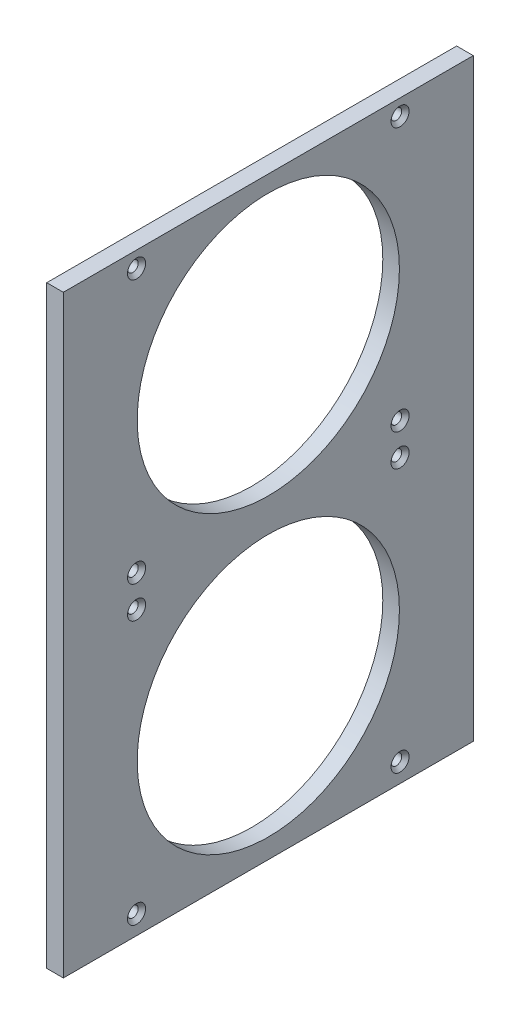
SolidWorks part; units mm, degrees
ref_plane "Front Plane" through (0, 0, 0) normal (0, 0, 1) x (1, 0, 0)
ref_plane "Top Plane" through (0, 0, 0) normal (0, 1, 0) x (1, 0, 0)
ref_plane "Right Plane" through (0, 0, 0) normal (1, 0, 0) x (0, 0, -1)
sketch "Sketch1" plane through (0, 0, 0) normal (0, 1, 0) x (1, 0, 0)
  line L1 (-83.25, 55.5) -> (83.25, 55.5)
  line L2 (-83.25, 55.5) -> (-83.25, -55.5)
  line L3 (-83.25, -55.5) -> (83.25, -55.5)
  line L4 (83.25, 55.5) -> (83.25, -55.5)
  line L5 (-83.25, 55.5) -> (83.25, -55.5) construction
  line L6 (-83.25, -55.5) -> (83.25, 55.5) construction
  point P0 (0, 0)
  dimension "D1" = 166.5
  dimension "D2" = 111
extrude "Boss-Extrude1" add sketch "Sketch1" along normal blind 30.5
shell "Shell1" thickness 4.5 removed face at (-83.25, 15.25, 0) removed face at (0, 30.5, 0)
sketch "Sketch2" plane through (0, 4.5, 0) normal (0, 1, 0) x (1, 0, 0)
  line L5 (78.75, 51) -> (-83.25, 51) construction
  line L6 (-78.25, 46) -> (78.75, 46)
  line L9 (-78.25, 46) -> (-78.25, -46)
  line L10 (-78.25, -46) -> (78.75, -46)
  line L11 (78.75, 46) -> (78.75, -46)
  line L12 (-83.25, -51) -> (78.75, -51) construction
  line L13 (-83.25, 51) -> (-83.25, -51) construction
  line L14 (78.75, -51) -> (78.75, 51) construction
  point P0 (0, 0)
  dimension "D1" = 5
  dimension "D2" = 5
  dimension "D3" = 5
extrude "Cut-Extrude1" cut sketch "Sketch2" against normal up to next
hole_wizard "Tap Drill for #6-32 Tap1" positions "Sketch4" profile "Sketch5" hole size "#6-32" standard "ANSI Inch" end condition up to next
sketch "Sketch4" plane through (0, 0, -55.5) normal (0, 0, -1) x (-1, 0, 0)
  line L0 (-78.75, 4.5) -> (83.25, 4.5) construction
  line L2 (-78.75, 30.5) -> (-78.75, 4.5) construction
  point P0 (47.66, 10.84)
  point P2 (-53.75, 10.84)
  dimension "D1" = 6.34
  dimension "D2" = 25
  dimension "D3" = 101.41
sketch "Sketch5" plane through (-47.66, 10.84, -55.5) normal (1, 0, 0) x (0, 1, 0)
  line L0 (0, 0) -> (0, 4.5)
  line L1 (0, 4.5) -> (1.4503, 4.5)
  line L2 (1.4503, 4.5) -> (1.4503, 0)
  line L5 (1.4503, 0) -> (0, 0)
  line L11 (0, -6.35) -> (0, 107.95) construction
  dimension "Thru Hole Dia." = 2.9007
  dimension "Thru Hole Depth" = 4.5
mirror "Mirror1" about plane through (0, 0, 0) normal (0, 0, 1) of "Tap Drill for #6-32 Tap1"
pattern_linear "LPattern1" count 8 spacing 30.5 along (0, 1, 0) of bodies 104
combine bodies "Combine1" operation type add bodies to combine 104 105
sketch "Sketch7" plane through (-83.25, 0, 0) normal (-1, 0, 0) x (0, 0, 1)
  line L1 (-51, 30.5) -> (51, 30.5)
  line L2 (-51, 30.5) -> (-51, 35)
  line L3 (-51, 35) -> (51, 35)
  line L4 (51, 30.5) -> (51, 35)
extrude "Cut-Extrude2" cut sketch "Sketch7" against normal up to surface (5 mm away) up to face at (-78.25, 32.75, 0)
combine bodies "Combine2" operation type add bodies to combine 109 110 112 111 114 108 113
sketch "Sketch8" plane through (-83.25, 0, 0) normal (-1, 0, 0) x (0, 0, 1)
  line L1 (-51, 61) -> (51, 61)
  line L2 (-51, 61) -> (-51, 218)
  line L3 (-51, 218) -> (51, 218)
  line L4 (51, 61) -> (51, 218)
extrude "Cut-Extrude3" cut sketch "Sketch8" against normal up to surface (5 mm away) up to face at (-78.25, 215.75, 0)
sketch "Sketch9" plane through (83.25, 0, 0) normal (1, 0, 0) x (0, 0, -1)
  line L0 (-55.5, 244) -> (55.5, 244) construction
  line L1 (-40, 244) -> (40, 244) construction
  line L2 (-40, 244) -> (-40, 4) construction
  line L3 (-40, 4) -> (40, 4) construction
  line L4 (40, 244) -> (40, 4) construction
  line L5 (0, 244) -> (0, 4) construction
  line L6 (-40, 164) -> (40, 164) construction
  line L7 (-40, 84) -> (40, 84) construction
  circle A0 centre (0, 204) radius 35.5
  circle A1 centre (0, 124) radius 35.5
  circle A2 centre (0, 44) radius 35.5
  dimension "D5" = 71
  dimension "D7" = 71
  dimension "D8" = 71
  dimension "D1" = 240
  dimension "D2" = 80
  dimension "D3" = 80
  dimension "D4" = 80
  dimension "D6" = 40
  dimension "D9" = 40
extrude "Cut-Extrude4" cut sketch "Sketch9" against normal up to next
sketch "Fan Dimensions" plane through (83.25, 0, 0) normal (1, 0, 0) x (0, 0, -1)
  line L0 (0, 239.5) -> (0, 168.5) construction
  line L1 (-40, 204) -> (40, 204) construction
  line L2 (-40, 244) -> (40, 244) construction
  line L3 (-40, 244) -> (-40, 164) construction
  line L4 (-40, 164) -> (40, 164) construction
  line L5 (40, 244) -> (40, 164) construction
  line L6 (-40, 244) -> (40, 164) construction
  line L7 (-40, 164) -> (40, 244) construction
  circle A0 centre (0, 204) radius 35.5 construction
  circle A1 centre (-35.675, 239.675) radius 2.175
  circle A2 centre (35.675, 239.675) radius 2.175
  circle A3 centre (35.675, 168.325) radius 2.175
  circle A4 centre (-35.675, 168.325) radius 2.175
  point P5 (0, 204)
  dimension "D2" = 80
  dimension "D3" = 4.35
  dimension "D1" = 80
  dimension "D4" = 4.325
hole_wizard "Tap Drill for #6-32 Tap2" positions "Sketch11" profile "Sketch12" hole size "#6-32" standard "ANSI Inch" end condition up to next
sketch "Sketch11" plane through (83.25, 0, 0) normal (1, 0, 0) x (0, 0, -1)
  point P0 (-35.675, 239.675)
  point P3 (35.675, 239.675)
  point P6 (35.675, 168.325)
  point P9 (-35.675, 168.325)
sketch "Sketch12" plane through (83.25, 239.675, 35.675) normal (0, 1, 0) x (0, 0, -1)
  line L0 (0, 0) -> (0, 4.5)
  line L1 (0, 4.5) -> (1.4503, 4.5)
  line L2 (1.4503, 4.5) -> (1.4503, 0)
  line L5 (1.4503, 0) -> (0, 0)
  line L11 (0, -6.35) -> (0, 107.95) construction
  dimension "Thru Hole Dia." = 2.9007
  dimension "Thru Hole Depth" = 4.5
ref_plane "Plane1" through (0, 164, 0) normal (0, 1, 0) x (1, 0, 0)
mirror "Mirror2" about plane through (0, 164, 0) normal (0, 1, 0) of "Tap Drill for #6-32 Tap2"
ref_plane "Plane2" through (0, 124, 0) normal (0, 1, 0) x (1, 0, 0)
mirror "Mirror3" about plane through (0, 124, 0) normal (0, 1, 0) of "Tap Drill for #6-32 Tap2"
sketch "Sketch13" plane through (0, 0, 0) normal (0, -1, 0) x (1, 0, 0)
  line L0 (83.25, 55.5) -> (83.25, -55.5) construction
  line L1 (-83.25, -55.5) -> (83.25, -55.5)
  line L2 (-83.25, -55.5) -> (-83.25, -147.5)
  line L3 (-83.25, -147.5) -> (83.25, -147.5)
  line L4 (83.25, -55.5) -> (83.25, -147.5)
  dimension "D1" = 92
extrude "Boss-Extrude2" add sketch "Sketch13" against normal blind 4.5
ref_plane "Plane3" through (0, 0, -101.5) normal (0, 0, -1) x (-1, 0, 0)
mirror "Mirror4" about plane through (0, 0, -101.5) normal (0, 0, -1) of bodies 122 125
sketch "Sketch17" plane through (-78.25, 0, 0) normal (-1, 0, 0) x (0, 0, 1)
  line L0 (-46, 35) -> (-51, 30.5)
  line L1 (-51, 30.5) -> (-46, 30.5)
  line L2 (-46, 30.5) -> (-46, 35)
  line L3 (-51, 61) -> (-46, 65.5)
  line L4 (-46, 65.5) -> (-46, 61)
  line L5 (-46, 61) -> (-51, 61)
  line L6 (-51, 91.5) -> (-46, 96)
  line L7 (-46, 96) -> (-46, 91.5)
  line L8 (-46, 91.5) -> (-51, 91.5)
  line L9 (-51, 122) -> (-46, 126.5)
  line L10 (-46, 126.5) -> (-46, 122)
  line L11 (-46, 122) -> (-51, 122)
  line L12 (-51, 152.5) -> (-46, 157)
  line L13 (-46, 157) -> (-46, 152.5)
  line L14 (-46, 152.5) -> (-51, 152.5)
  line L15 (-51, 183) -> (-46, 187.5)
  line L16 (-46, 187.5) -> (-46, 183)
  line L17 (-46, 183) -> (-51, 183)
  line L18 (-51, 213.5) -> (-46, 218)
  line L19 (-46, 218) -> (-46, 213.5)
  line L20 (-46, 213.5) -> (-51, 213.5)
extrude "Cut-Extrude7" cut sketch "Sketch17" against normal up to surface (157 mm away) up to face at (78.75, 8.325, 37.1253)
mirror "Mirror5" about plane through (0, 0, 0) normal (0, 0, 1) of "Cut-Extrude7"
mirror "Mirror6" about plane through (0, 0, -101.5) normal (0, 0, -1) of "Mirror5", "Cut-Extrude7"
sketch "Sketch31" plane through (0, 4.5, 0) normal (0, 1, 0) x (1, 0, 0)
  line L1 (-83.25, 254) -> (-78.25, 254)
  line L2 (-83.25, 254) -> (-83.25, 152)
  line L3 (-83.25, 152) -> (-78.25, 152)
  line L4 (-78.25, 254) -> (-78.25, 152)
  line L5 (-83.25, 51) -> (-78.25, 51)
  line L6 (-83.25, 51) -> (-83.25, -51)
  line L7 (-83.25, -51) -> (-78.25, -51)
  line L8 (-78.25, 51) -> (-78.25, -51)
extrude "Cut-Extrude11" cut sketch "Sketch31" against normal up to next
sketch "Sketch33" plane through (83.25, 0, 0) normal (1, 0, 0) x (0, 0, -1)
  line L1 (147.5, 4.5) -> (143, 4.5)
  line L2 (147.5, 4.5) -> (147.5, 153.7)
  line L3 (147.5, 153.7) -> (143, 153.7)
  line L4 (143, 4.5) -> (143, 153.7)
  dimension "D1" = 4.5
  dimension "D2" = 149.2
extrude "Boss-Extrude3" add sketch "Sketch33" against normal blind 4.5
pattern_linear "LPattern2" count 3 spacing 81 along (-1, 0, 0) of "Boss-Extrude3"
sketch "Sketch34" plane through (-83.25, 0, 0) normal (-1, 0, 0) x (0, 0, 1)
  line L0 (-147.5, 153.7) -> (-147.5, 0) construction
  line L1 (-152, 0) -> (-51, 0) construction
  line L2 (-143, 25) -> (-147.5, 25)
  line L3 (-143, 153.7) -> (-143, 4.5) construction
  line L4 (-147.5, 25) -> (-147.5, 76.85)
  line L5 (-147.5, 76.85) -> (-143, 81.35)
  line L6 (-143, 81.35) -> (-143, 25)
  line L7 (-143, 89.35) -> (-147.5, 89.35)
  line L8 (-147.5, 89.35) -> (-147.5, 141.2)
  line L9 (-147.5, 141.2) -> (-143, 145.7)
  line L10 (-143, 145.7) -> (-143, 89.35)
  line L11 (-147.5, 153.7) -> (-143, 153.7) construction
  line L12 (-55.5, 4.5) -> (-143, 4.5) construction
  line L13 (-147.5, 25) -> (-143, 25)
  line L14 (-147.5, 25) -> (-147.5, 13.5)
  line L15 (-147.5, 13.5) -> (-143, 13.5)
  line L16 (-143, 25) -> (-143, 13.5)
  line M20 (-143, 4.5) -> (-143, 153.7)
  dimension "D1" = 45
  dimension "D2" = 45
  dimension "D3" = 8
  dimension "D4" = 8
  dimension "D5" = 9
extrude "Cut-Extrude12" cut sketch "Sketch34" against normal up to surface (85.5 mm away) contours L5 L4 L2 M20 | L14 L15 L2 M20 | L10 L7 L8 L9 up to face at (2.25, 79.1, -145.25)
sketch "Sketch35" plane through (78.75, 0, 0) normal (-1, 0, 0) x (0, 0, 1)
  line L4 (-147.5, 153.7) -> (-147.5, 4.5)
  line L5 (-147.5, 4.5) -> (-143, 4.5)
  line L6 (-143, 4.5) -> (-143, 153.7)
  line L7 (-143, 153.7) -> (-147.5, 153.7)
  line L8 (-147.5, 153.7) -> (-147.5, 4.5)
  line L9 (-147.5, 4.5) -> (-143, 4.5)
  line L10 (-143, 4.5) -> (-143, 153.7)
  line L11 (-143, 153.7) -> (-147.5, 153.7)
  dimension "D1" = 0
extrude "Boss-Extrude4" add sketch "Sketch35" along normal blind 4.5
sketch "Sketch36" plane through (83.25, 0, 0) normal (1, 0, 0) x (0, 0, -1)
  line L0 (147.5, 153.7) -> (55.5, 153.7) construction
  line L1 (55.5, 4.5) -> (69.5, 4.5)
  line L2 (55.5, 4.5) -> (55.5, 42.5)
  line L3 (55.5, 42.5) -> (69.5, 42.5)
  line L4 (69.5, 4.5) -> (69.5, 42.5)
  line L5 (55.5, 244) -> (55.5, 4.5) construction
  line L7 (55.5, 153.7) -> (79.5, 153.7)
  line L8 (55.5, 153.7) -> (55.5, 141.7)
  line L9 (55.5, 141.7) -> (79.5, 141.7)
  line L10 (79.5, 153.7) -> (79.5, 141.7)
  line L11 (143, 153.7) -> (131, 153.7)
  line L12 (143, 153.7) -> (143, 139.7)
  line L13 (143, 139.7) -> (131, 139.7)
  line L14 (131, 153.7) -> (131, 139.7)
  line L15 (143, 4.5) -> (129, 4.5)
  line L16 (143, 4.5) -> (143, 16.5)
  line L17 (143, 16.5) -> (129, 16.5)
  line L18 (129, 4.5) -> (129, 16.5)
  dimension "D1" = 14
  dimension "D2" = 38
  dimension "D3" = 24
  dimension "D4" = 12
  dimension "D5" = 12
  dimension "D6" = 14
  dimension "D7" = 14
  dimension "D8" = 12
extrude "Boss-Extrude5" add sketch "Sketch36" against normal blind 4.5
sketch "Sketch37" plane through (83.25, 0, 0) normal (1, 0, 0) x (0, 0, -1)
  line L0 (55.5, 244) -> (55.5, 153.7) construction
  line L1 (79.5, 153.7) -> (55.5, 153.7) construction
  line L2 (143, 139.7) -> (143, 16.5) construction
  line L3 (55.5, 141.7) -> (55.5, 42.5) construction
  line L4 (129, 4.5) -> (69.5, 4.5) construction
  circle A0 centre (71.32, 147.92) radius 1.45
  circle A1 centre (137.68, 147.92) radius 1.45
  circle A2 centre (61.57, 34.51) radius 1.45
  circle A3 centre (137.55, 10.15) radius 1.45
  dimension "D1" = 2.9
  dimension "D4" = 2.9
  dimension "D6" = 2.9
  dimension "D9" = 2.9
  dimension "D2" = 15.82
  dimension "D3" = 5.78
  dimension "D5" = 5.32
  dimension "D7" = 6.07
  dimension "D8" = 30.01
  dimension "D10" = 5.65
  dimension "D11" = 5.45
extrude "Cut-Extrude13" cut sketch "Sketch37" against normal up to next
sketch "Sketch38" plane through (83.25, 0, 0) normal (1, 0, 0) x (0, 0, -1)
  line L0 (79.5, 141.7) -> (55.5, 117.7)
  line L1 (55.5, 141.7) -> (55.5, 42.5) construction
  line L2 (55.5, 117.7) -> (55.5, 141.7)
  line L3 (55.5, 141.7) -> (79.5, 141.7)
  line L4 (131, 139.7) -> (143, 127.7)
  line L5 (143, 139.7) -> (143, 16.5) construction
  line L6 (143, 127.7) -> (143, 139.7)
  line L7 (143, 139.7) -> (131, 139.7)
  dimension "D1" = 45
  dimension "D2" = 45
extrude "Boss-Extrude6" add sketch "Sketch38" along normal up to surface (4.5 mm away)
sketch "Sketch39" plane through (83.25, 0, 0) normal (1, 0, 0) x (0, 0, -1)
  circle A0 centre (71.32, 147.92) radius 3.5
  circle A1 centre (137.68, 147.92) radius 3.5
  circle A2 centre (137.55, 10.15) radius 3.5
  circle A3 centre (61.57, 34.51) radius 3.5
  dimension "D1" = 7
  dimension "D2" = 7
  dimension "D3" = 7
  dimension "D4" = 7
extrude "Cut-Extrude14" cut sketch "Sketch39" against normal blind 2.5 draft 39
chamfer "Chamfer1" distance 4.5 angle 45 4 edges at (81, 16.5, -129) (81, 153.7, -131) (81, 153.7, -79.5) (81, 42.5, -69.5)
sketch "Sketch41" plane through (0, 0, 0) normal (0, -1, 0) x (1, 0, 0)
  line L1 (-83.25, 55.5) -> (83.25, 55.5)
  line L2 (-83.25, 55.5) -> (-83.25, -258.5)
  line L3 (-83.25, -258.5) -> (83.25, -258.5)
  line L4 (83.25, 55.5) -> (83.25, -258.5)
extrude "Boss-Extrude7" add sketch "Sketch41" along normal blind 4.5
sketch "Sketch42" plane through (0, 0, 0) normal (0, 1, 0) x (1, 0, 0)
  line L0 (-43.855, 38) -> (43.855, 38)
  line L1 (45.3708, 32.4111) -> (1.5158, 6.7345)
  line L2 (-1.5158, 6.7345) -> (-45.3708, 32.4111)
  line L3 (10.2688, 2.5889) -> (66.2342, 35.3561)
  line L4 (70.75, 32.7672) -> (70.75, -32.7672)
  line L5 (66.2342, -35.3561) -> (10.2688, -2.5889)
  line L7 (78.75, -51) -> (78.75, 51) construction
  line L8 (78.75, 46) -> (-78.25, 46) construction
  line L9 (78.75, -46) -> (-78.25, -46) construction
  line L10 (0, 5.847) -> (0, 0) construction
  line L11 (0, 0) -> (5.847, 0) construction
  line L12 (-83.25, 0) -> (70.75, 0) construction
  line L13 (-83.25, -51) -> (-83.25, 51) construction
  line L14 (0, 38) -> (0.25, -46) construction
  line L15 (-78.25, -46) -> (78.75, -46) construction
  line L16 (45.3708, -32.4111) -> (1.5158, -6.7345)
  line L17 (-43.855, -38) -> (43.855, -38)
  line L18 (-1.5158, -6.7345) -> (-45.3708, -32.4111)
  line L19 (-70.7176, 32.3461) -> (-70.3275, -33.187)
  line L20 (-10.0578, 2.5284) -> (-66.2173, 34.9619)
  line L21 (-65.7964, -35.749) -> (-10.027, -2.6493)
  arc A0 (70.75, -32.7672) -> (66.2342, -35.3561) centre (67.75, -32.7672) cw
  arc A1 (70.75, 32.7672) -> (66.2342, 35.3561) centre (67.75, 32.7672) ccw
  arc A2 (10.2688, -2.5889) -> (10.2688, 2.5889) centre (11.7845, 0) cw
  arc A3 (-1.5158, 6.7345) -> (1.5158, 6.7345) centre (0, 9.3234) ccw
  arc A4 (-45.3708, 32.4111) -> (-43.855, 38) centre (-43.855, 35) cw
  arc A5 (45.3708, 32.4111) -> (43.855, 38) centre (43.855, 35) ccw
  arc A6 (45.3708, -32.4111) -> (43.855, -38) centre (43.855, -35) cw
  arc A7 (-1.5158, -6.7345) -> (1.5158, -6.7345) centre (0, -9.3234) cw
  arc A8 (-45.3708, -32.4111) -> (-43.855, -38) centre (-43.855, -35) ccw
  arc A9 (-70.7176, 32.3461) -> (-66.2173, 34.9619) centre (-67.7177, 32.364) cw
  arc A10 (-70.3275, -33.187) -> (-65.7964, -35.749) centre (-67.3276, -33.1692) ccw
  arc A11 (-10.027, -2.6493) -> (-10.0578, 2.5284) centre (-11.5581, -0.0695) ccw
  point P24 (70.75, -38)
  dimension "D5" = 3
  dimension "D1" = 8
  dimension "D2" = 8
  dimension "D3" = 8
  dimension "D4" = 8
  dimension "D6" = 5.847
extrude "Cut-Extrude15" cut sketch "Sketch42" against normal up to next
mirror "Mirror7" about plane through (0, 0, -101.5) normal (0, 0, -1) of "Cut-Extrude15"
chamfer "Chamfer2" distance 2.7 angle 39 16 edges at (55.2003, 10.84, 55.5) (-46.2097, 224.34, 55.5) (-46.2097, 193.84, 55.5) (-46.2097, 163.34, 55.5) (-46.2097, 132.84, 55.5) (-46.2097, 102.34, 55.5) (-46.2097, 71.84, 55.5) (-46.2097, 41.34, 55.5) (55.2003, 224.34, 55.5) (55.2003, 193.84, 55.5) (55.2003, 163.34, 55.5) (55.2003, 132.84, 55.5) (55.2003, 71.84, 55.5) (55.2003, 41.34, 55.5) (-46.2097, 10.84, 55.5) (55.2003, 102.34, 55.5)
chamfer "Chamfer3" distance 2.7 angle 39 16 edges at (-49.1103, 10.84, -55.5) (-49.1103, 41.34, -55.5) (-49.1103, 71.84, -55.5) (-49.1103, 102.34, -55.5) (-49.1103, 132.84, -55.5) (-49.1103, 163.34, -55.5) (-49.1103, 193.84, -55.5) (-49.1103, 224.34, -55.5) (52.2997, 10.84, -55.5) (52.2997, 41.34, -55.5) (52.2997, 71.84, -55.5) (52.2997, 102.34, -55.5) (52.2997, 132.84, -55.5) (52.2997, 163.34, -55.5) (52.2997, 193.84, -55.5) (52.2997, 224.34, -55.5)
chamfer "Chamfer4" distance 2.7 angle 39 32 edges at (52.2997, 10.84, -147.5) (52.2997, 41.34, -147.5) (52.2997, 71.84, -147.5) (52.2997, 102.34, -147.5) (52.2997, 132.84, -147.5) (52.2997, 224.34, -147.5) (52.2997, 193.84, -147.5) (52.2997, 163.34, -147.5) (-49.1103, 224.34, -147.5) (-49.1103, 193.84, -147.5) (-49.1103, 163.34, -147.5) (-49.1103, 132.84, -147.5) (-49.1103, 102.34, -147.5) (-49.1103, 71.84, -147.5) (-49.1103, 41.34, -147.5) (-49.1103, 10.84, -147.5) (-46.2097, 224.34, -258.5) (-46.2097, 193.84, -258.5) (-46.2097, 163.34, -258.5) (-46.2097, 132.84, -258.5) (-46.2097, 102.34, -258.5) (-46.2097, 71.84, -258.5) (-46.2097, 41.34, -258.5) (-46.2097, 10.84, -258.5) (55.2003, 10.84, -258.5) (55.2003, 41.34, -258.5) (55.2003, 71.84, -258.5) (55.2003, 102.34, -258.5) (55.2003, 132.84, -258.5) (55.2003, 163.34, -258.5) (55.2003, 193.84, -258.5) (55.2003, 224.34, -258.5)
chamfer "Chamfer5" distance 1 angle 45 24 edges at (83.25, 239.675, -165.8747) (83.25, 239.675, -237.2247) (83.25, 168.325, -237.2247) (83.25, 168.325, -165.8747) (83.25, 159.675, -165.8747) (83.25, 159.675, -237.2247) (83.25, 88.325, -237.2247) (83.25, 88.325, -165.8747) (83.25, 79.675, -165.8747) (83.25, 79.675, -237.2247) (83.25, 8.325, -237.2247) (83.25, 8.325, -165.8747) (83.25, 8.325, 34.2247) (83.25, 88.325, 34.2247) (83.25, 79.675, 34.2247) (83.25, 88.325, -37.1253) (83.25, 79.675, -37.1253) (83.25, 8.325, -37.1253) (83.25, 159.675, -37.1253) (83.25, 168.325, -37.1253) (83.25, 159.675, 34.2247) (83.25, 168.325, 34.2247) (83.25, 239.675, -37.1253) (83.25, 239.675, 34.2247)
fillet "Fillet1" radius 4 3 edges at (38.25, 4.5, -147.5) (-40.5, 4.5, -147.5) (-2.25, 4.5, -55.5)
fillet "Fillet2" radius 4 4 edges at (0.25, 0, 46) (0.25, 0, -46) (0.25, 0, -157) (0.25, 0, -249)
fillet "Fillet3" radius 4 10 edges at (78.75, 4.25, -157) (78.75, 1.1716, -158.1716) (78.75, 4.25, -249) (78.75, 1.1716, -247.8284) (78.75, 4.25, -46) (78.75, 1.1716, -44.8284) (78.75, 4.25, 46) (78.75, 1.1716, 44.8284) (78.75, 0, -203) (78.75, 0, 0)
chamfer "Chamfer6" distance 20 angle 45 4 edges at (-83.25, 244, -149.75) (-83.25, 244, -256.25) (-83.25, 244, 53.25) (-83.25, 244, -53.25)
sketch "Sketch44" plane through (0, 0, -152) normal (0, 0, -1) x (-1, 0, 0)
  line L1 (-78.75, 244) -> (83.25, 244)
  line L2 (-78.75, 244) -> (-78.75, -4.5)
  line L3 (-78.75, -4.5) -> (83.25, -4.5)
  line L4 (83.25, 244) -> (83.25, -4.5)
extrude "Cut-Extrude16" cut sketch "Sketch44" against normal through all both and the other way through all
sketch "Sketch45" plane through (83.25, 0, 0) normal (1, 0, 0) x (0, 0, -1)
  line L1 (55.5, 244) -> (258.5, 244)
  line L2 (55.5, 244) -> (55.5, -4.5)
  line L3 (55.5, -4.5) -> (258.5, -4.5)
  line L4 (258.5, 244) -> (258.5, -4.5)
extrude "Cut-Extrude17" cut sketch "Sketch45" against normal through all both and the other way through all
sketch "Sketch46" plane through (83.25, 0, 0) normal (1, 0, 0) x (0, 0, -1)
  line L0 (-55.5, 244) -> (-55.5, -4.5) construction
  line L1 (55.5, -4.5) -> (-55.5, -4.5)
  line L2 (55.5, -4.5) -> (55.5, 83.1962)
  line L3 (55.5, 83.1962) -> (-55.5, 83.1962)
  line L4 (-55.5, -4.5) -> (-55.5, 83.1962)
extrude "Cut-Extrude18" cut sketch "Sketch46" against normal through all both and the other way through all
equation "\"Drive Lenght\"= 162"
equation "\"Drive Width\"= 102"
equation "\"Drive Thickness\"= 25.5"
equation "\"D1@Sketch1\"=\"Drive Lenght\"+\"Spacer\""
equation "\"D2@Sketch1\"=\"Drive Width\" +\"Spacer\"*2"
equation "\"D1@Boss-Extrude1\"=\"Drive Thickness\"+5"
equation "\"D1@Sketch2\"=5"
equation "\"D2@Sketch2\"=5"
equation "\"D3@Sketch2\"=5"
equation "\"Spacer\"= 4.5"
equation "\"Drive Hole from botton\"= 6.34"
equation "\"Between Drive holes\"= 101.41"
equation "\"Drive hole to fron\" = 25"
equation "\"D1@Sketch4\"=\"Drive Hole from botton\""
equation "\"D2@Sketch4\"= \"Drive hole to fron\""
equation "\"D3@Sketch4\"=\"Between Drive holes\""
equation "\"D3@LPattern1\"=\"Drive Thickness\"+5 "
equation "\"D6@Sketch9\"=40"
equation "\"D7@Sketch9\"=\"D5@Sketch9\""
equation "\"D8@Sketch9\"=\"D5@Sketch9\""
equation "\"D2@Fan Dimensions\" = \"D1@Fan Dimensions\""
equation "\"Power Supply Thickness\"= 87.5"
equation "\"D1@Boss-Extrude2\"=\"Spacer\""
equation "\"D1@Sketch13\"= \"Power Supply Thickness\" + \"Spacer\""
equation "\"Power Supply Height\"= 149.2"
equation "\"Mount Hole Diameter\" = 2.9"
equation "\"D1@Sketch33\"=\"Spacer\""
equation "\"D2@Sketch33\"=\"Power Supply Height\""
equation "\"D1@Boss-Extrude3\"=\"Spacer\""
equation "\"D3@LPattern2\"=\"Drive Lenght\"/2"
equation "\"D1@Boss-Extrude5\"=\"Spacer\""
equation "\"D1@Sketch37\"=\"Mount Hole Diameter\""
equation "\"D2@Sketch37\"=14.37 + \"Mount Hole Diameter\"/2"
equation "\"D3@Sketch37\"=4.33 + \"Mount Hole Diameter\"/2"
equation "\"D4@Sketch37\"=\"Mount Hole Diameter\""
equation "\"D5@Sketch37\"=3.87 +\"Mount Hole Diameter\"/2"
equation "\"D6@Sketch37\"=\"Mount Hole Diameter\""
equation "\"D7@Sketch37\"=4.62 +\"Mount Hole Diameter\"/2"
equation "\"D8@Sketch37\"=28.56 +\"Mount Hole Diameter\"/2"
equation "\"D9@Sketch37\"=\"Mount Hole Diameter\""
equation "\"D10@Sketch37\"=4.2 +\"Mount Hole Diameter\"/2"
equation "\"D2@Sketch39\"=\"D1@Sketch39\""
equation "\"D3@Sketch39\"=\"D1@Sketch39\""
equation "\"D4@Sketch39\"=\"D3@Sketch39\""
equation "\"Counter Sink Depth\"= 2.5"
equation "\"D1@Cut-Extrude14\"=\"Counter Sink Depth\""
equation "\"D11@Sketch37\"=4 +\"Mount Hole Diameter\"/2"
equation "\"D1@Chamfer1\"=\"Spacer\""
